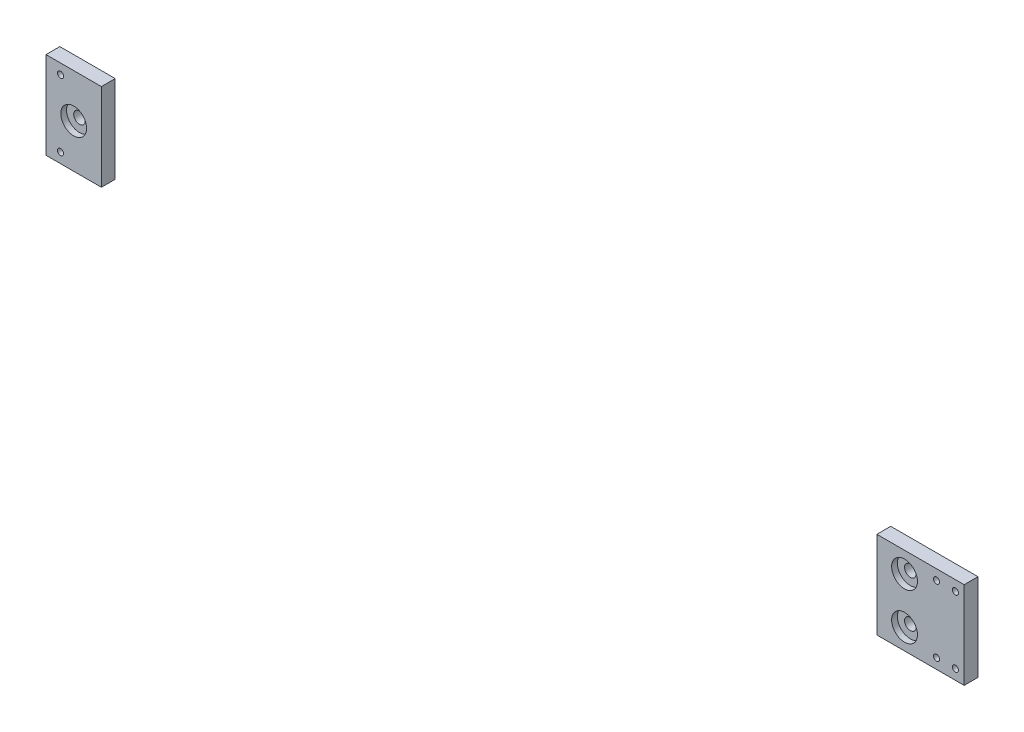
SolidWorks part; units mm, degrees
other "Front Bracket"
other "Rear Bracket"
ref_plane "Front Plane" through (0, 0, 0) normal (0, 0, 1) x (1, 0, 0)
ref_plane "Top Plane" through (0, 0, 0) normal (0, 1, 0) x (1, 0, 0)
ref_plane "Right Plane" through (0, 0, 0) normal (1, 0, 0) x (0, 0, -1)
sketch "Sketch2" plane through (0, 0, 0) normal (0, 0, 1) x (1, 0, 0)
  line L0 (304.725, 30) -> (276.237, 30)
  line L1 (-295.275, -30) -> (-257.175, -30)
  line L2 (-295.275, -30) -> (-295.275, 30)
  line L3 (-295.275, 30) -> (-257.175, 30)
  line L4 (-257.175, -30) -> (-257.175, 30)
  line L5 (-295.275, -30) -> (-257.175, 30) construction
  line L6 (-295.275, 30) -> (-257.175, -30) construction
  line L7 (304.725, -30) -> (342.825, -30)
  line L8 (304.725, -30) -> (304.725, 30) construction
  line L9 (304.725, 30) -> (342.825, 30)
  line L10 (342.825, -30) -> (342.825, 30)
  line L11 (304.725, -30) -> (342.825, 30) construction
  line L12 (304.725, 30) -> (342.825, -30) construction
  line L13 (276.237, -152.388) -> (276.237, 152.412) construction
  line L14 (276.237, 30) -> (276.237, -30)
  line L15 (276.237, -30) -> (304.725, -30)
  circle A0 centre (-276.225, 0) radius 3.9688
  circle A1 centre (-276.225, 0) radius 8.89
  circle A2 centre (323.775, 0) radius 3.9688 construction
  circle A3 centre (323.775, 0) radius 8.89 construction
  point P0 (-276.225, 0)
  point P9 (323.775, 0)
  dimension "D3" = 17.78
  dimension "D4" = 7.9375
  dimension "D1" = 38.1
  dimension "D2" = 60
  dimension "D6" = 600
  dimension "D5" = 2
extrude "Main Extrusion" add sketch "Sketch2" along normal blind 5.5575 contours L1 L4 L3 L2 A1 | A1 A0 | L7 L10 L9 L8 A3 | A3 A2 region at (309.531, 0, 0) region at (-294.5643, 0, 0) region at (-284.8636, 0, 0)
extrude "Counterbore extrusion" add sketch "Sketch2<3>" along normal blind 9.525 contours L1 L4 L3 L2 A1 | L7 L10 L9 L8 A3 region at (309.531, 0, 0) region at (-294.5643, 0, 0)
sketch "Sketch2<3>" plane through (0, 0, 0) normal (0, 0, 1) x (1, 0, 0) same geometry as "Sketch2"
sketch "Sketch3" plane through (0, 0, 9.525) normal (0, 0, 1) x (1, 0, 0)
  line L0 (-295.275, 0) -> (-257.175, 0) construction
  line L2 (-257.175, -30) -> (-257.175, 30) construction
  circle A0 centre (-285.275, 23) radius 2.1
  circle A1 centre (-285.275, -23) radius 2.1
  point P6 (-276.225, 0)
  dimension "D1" = 4.2
  dimension "D2" = 46
  dimension "D3" = 10
extrude "M5 Threaded holse for front bracket" cut sketch "Sketch3" against normal up to surface (9.525 mm away)
sketch "Sketch5" plane through (0, 0, 9.525) normal (0, 0, 1) x (1, 0, 0)
  line L0 (317.275, 23) -> (330.275, 23) construction
  line L1 (317.275, 23) -> (317.275, -23) construction
  circle A0 centre (317.275, 23) radius 2.1
  circle A1 centre (330.275, 23) radius 2.1
  circle A2 centre (330.275, -23) radius 2.1
  circle A3 centre (317.275, -23) radius 2.1
  point P0 (323.775, 0)
  point P5 (323.775, 23)
  point P6 (317.275, 0)
  dimension "D6" = 4.2
  dimension "D3" = 90
  dimension "D4" = 13
  dimension "D5" = 46
  dimension "D1" = 2
  dimension "D2" = 2
extrude "M5 Threaded holes for bracket" cut sketch "Sketch5" against normal up to surface (9.525 mm away)
sketch "Sketch6" plane through (0, 0, 9.525) normal (0, 0, 1) x (1, 0, 0)
  line L0 (295.275, -171.45) -> (295.275, 171.45) construction
  line L1 (295.275, -171.45) -> (295.275, 171.45) construction
  line L2 (13.75, 0) -> (-13.75, 0) construction
  circle A0 centre (295.275, 15.875) radius 8.89
  circle A1 centre (295.275, 15.875) radius 3.9688
  circle A2 centre (323.775, 0) radius 8.89 construction
  circle A3 centre (323.775, 0) radius 3.9688 construction
  circle A4 centre (295.275, -15.875) radius 3.9688
  circle A5 centre (295.275, -15.875) radius 8.89
  dimension "D1" = 31.75
extrude "centre bore" cut sketch "Sketch6" against normal through all contours L1 A1 | A1 L1 | L1 A4 | A4 L1 region at (293.5906, -15.875, 9.525) region at (296.9594, -15.875, 9.525) region at (293.5906, 15.875, 9.525) region at (296.9594, 15.875, 9.525)
extrude "counterbore" cut sketch "Sketch6<3>" against normal offset from surface (3.9675 mm away) 5.5575
sketch "Sketch6<3>" plane through (0, 0, 9.525) normal (0, 0, 1) x (1, 0, 0) same geometry as "Sketch6"
sketch "Sketch7" plane through (0, 0, 9.525) normal (0, 0, 1) x (1, 0, 0)
  line L1 (342.825, 30) -> (336.275, 30)
  line L2 (342.825, 30) -> (342.825, -30)
  line L3 (342.825, -30) -> (336.275, -30)
  line L4 (336.275, 30) -> (336.275, -30)
extrude "stupid cut" cut sketch "Sketch7" against normal through all
